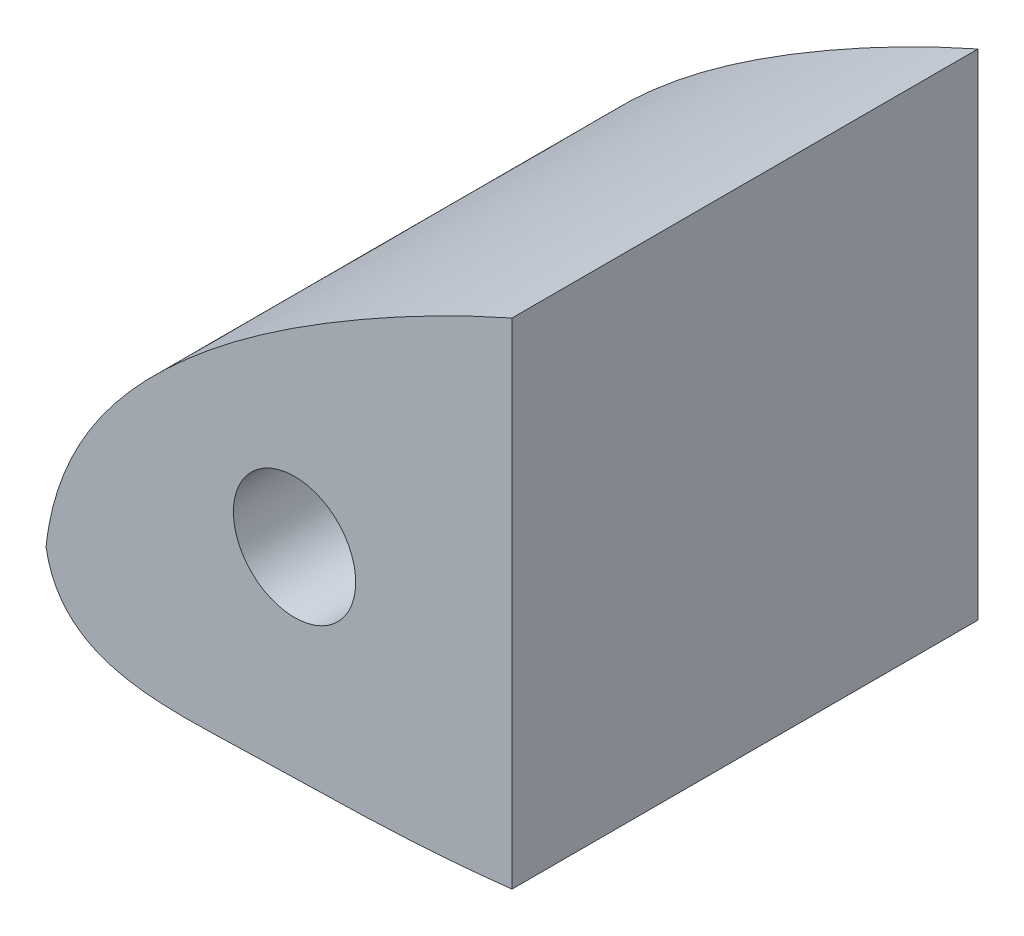
SolidWorks part; units mm, degrees
ref_plane "Front Plane" through (0, 0, 0) normal (0, 0, 1) x (1, 0, 0)
ref_plane "Top Plane" through (0, 0, 0) normal (0, 1, 0) x (1, 0, 0)
ref_plane "Right Plane" through (0, 0, 0) normal (1, 0, 0) x (0, 0, -1)
sketch "Sketch1" plane through (0, 0, 0) normal (0, 0, 1) x (1, 0, 0)
  spline S0 degree 3 poles (0.0006, 0.0001) (0.8106, 7.3592) (8.6491, 17.8566) (26.2867, 29.9752) (52.1111, 42.0692) (89.5976, 49.2908) (131.4008, 47.8848) (173.2567, 40.0411) (217.9611, 29.613) (256.9521, 19.5289) (290.3598, 8.711) (301.2732, 4.3828) (314.8169, -0.5162) (309.8463, 0.0001) knots 0 0 0 0 0.060864 0.113688 0.188609 0.312909 0.448482 0.557612 0.691544 0.852438 0.929756 0.976058 1 1 1 1
  spline S1 degree 3 poles (309.8463, 0.0001) (303.9568, 1.471) (293.9895, 2.094) (276.264, 4.5144) (260.8463, 5.4274) (235.8588, 7.8703) (205.1014, 8.8381) (157.7186, 9.0307) (110.4973, 6.1815) (66.5062, -0.5867) (36.4547, -6.0985) (15.3166, -6.1891) (1.2307, -6.9241) (0.0006, 0.0001) knots 0 0 0 0 0.057787 0.095275 0.171021 0.205339 0.335319 0.464904 0.658702 0.785512 0.893517 0.943092 1 1 1 1
extrude "Boss-Extrude1" add sketch "Sketch1" along normal blind 38.1
sketch "Sketch2" plane through (0, 0, 38.1) normal (0, 0, 1) x (1, 0, 0)
  circle A0 centre (20.32, 10.16) radius 5
  circle A1 centre (227.2963, 19.0501) radius 3.175
  dimension "D2" = 10
  dimension "D3" = 6.35
  dimension "D6" = 20.32
  dimension "D1" = 82.55
  dimension "D4" = 19.05
  dimension "D5" = 10.16
extrude "Cut-Extrude1" cut sketch "Sketch2" against normal through all
sketch "Sketch3" plane through (0, 0, 38.1) normal (0, 0, 1) x (1, 0, 0)
  line L1 (38.1, 71.718) -> (331.2889, 71.718)
  line L2 (38.1, 71.718) -> (38.1, -66.2532)
  line L3 (38.1, -66.2532) -> (331.2889, -66.2532)
  line L4 (331.2889, 71.718) -> (331.2889, -66.2532)
  dimension "D1" = 38.1
extrude "Cut-Extrude2" cut sketch "Sketch3" against normal through all
sketch "Sketch4" plane through (0, 0, 0) normal (0, 0, -1) x (-1, 0, 0)
  circle A0 centre (-20.32, 10.16) radius 7
  dimension "D1" = 14
extrude "Cut-Extrude3" cut sketch "Sketch4" against normal blind 3.175
